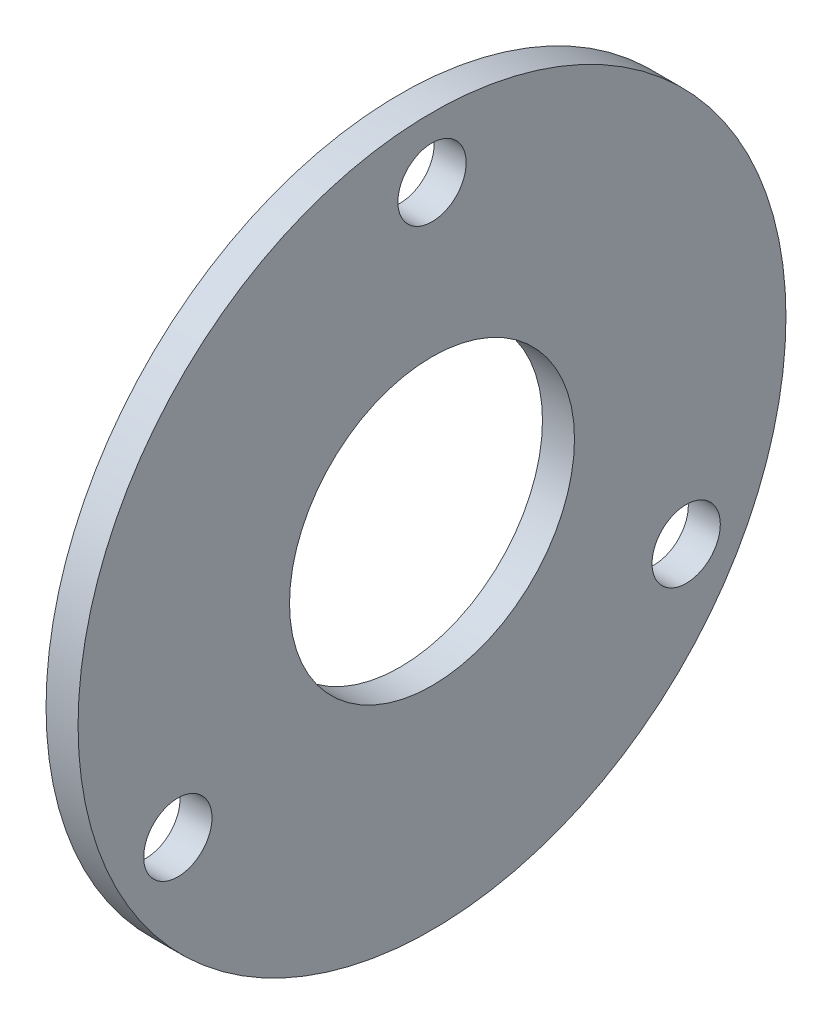
SolidWorks part; units mm, degrees
ref_plane "Płaszczyzna przednia" through (0, 0, 0) normal (0, 0, 1) x (1, 0, 0)
ref_plane "Płaszczyzna górna" through (0, 0, 0) normal (0, 1, 0) x (1, 0, 0)
ref_plane "Płaszczyzna prawa" through (0, 0, 0) normal (1, 0, 0) x (0, 0, -1)
sketch "Szkic1" plane through (0, 0, 0) normal (0, 0, 1) x (1, 0, 0)
  line L0 (0, 0) -> (-56.1578, 0)
  line L11 (-31.5025, 13.351) -> (-31.5025, 33.166)
  line L12 (-31.5025, 13.351) -> (-31.5025, 0)
  line L13 (-28.5025, 0) -> (-28.5025, 33.166)
  line L15 (-31.5025, 33.166) -> (-28.5025, 33.166)
  line L16 (-31.5025, 13.351) -> (-28.5025, 13.351)
revolve "Obrót2" add sketch "Szkic1" angle 360 about L0 region at (-30.0025, 23.2585, 0)
sketch "Szkic2" plane through (-28.5025, 0, 0) normal (1, 0, 0) x (0, 0, -1)
  line L0 (0, 0) -> (0, 27.5)
  circle A0 centre (0, 27.5) radius 3.2
  circle A1 centre (23.8157, -13.75) radius 3.2
  circle A2 centre (-23.8157, -13.75) radius 3.2
  point P11 (0, 0)
  dimension "D1" = 3
extrude "Wytnij-wyciągnięcie1" cut sketch "Szkic2" against normal through all contours A0 | A1 | A2 region at (-28.5025, 25.3013, -2.1987) region at (-28.5025, -13.75, -23.8157) region at (-28.5025, -13.75, 23.8157)
